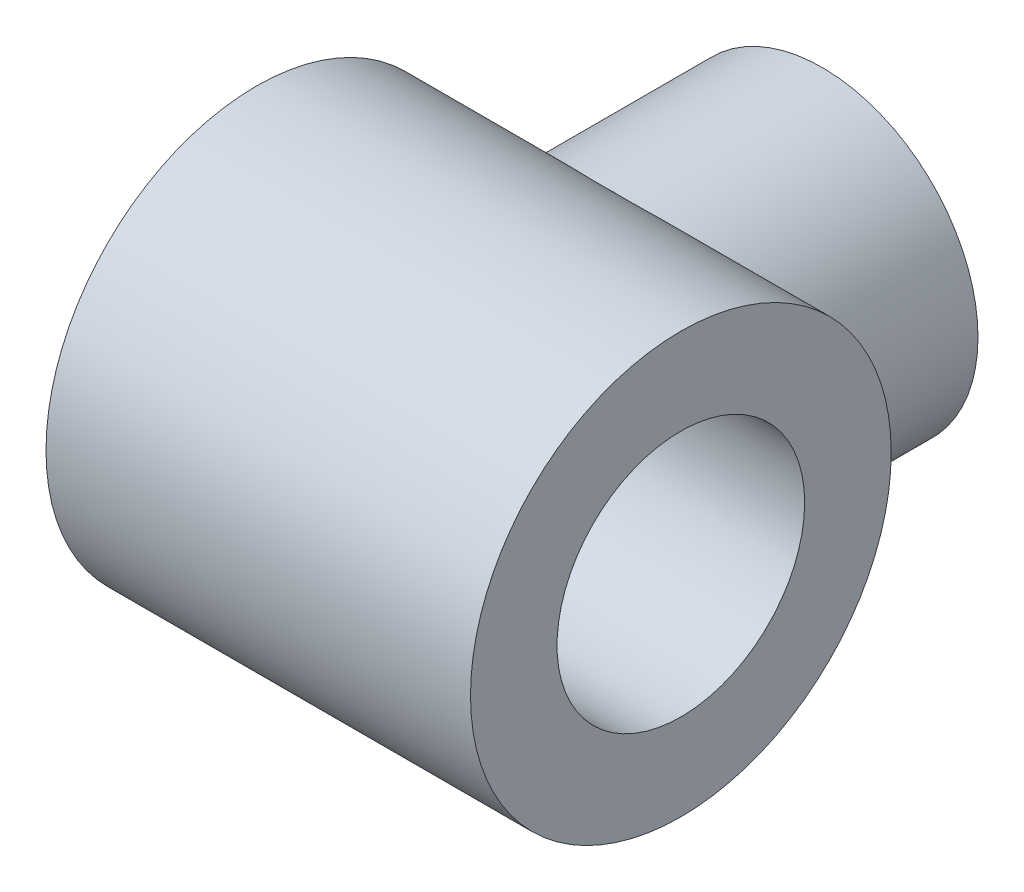
SolidWorks part; units mm, degrees
material "ABS"
ref_plane "前视基准面" through (0, 0, 0) normal (0, 0, 1) x (1, 0, 0)
ref_plane "上视基准面" through (0, 0, 0) normal (0, 1, 0) x (1, 0, 0)
ref_plane "右视基准面" through (0, 0, 0) normal (1, 0, 0) x (0, 0, -1)
sketch "草图1" plane through (0, 0, 0) normal (0, 0, 1) x (1, 0, 0)
  circle A0 centre (0, 0) radius 1.2
  circle A1 centre (0, 0) radius 2.2
  dimension "D1" = 2.4
  dimension "D2" = 4.4
extrude "凸台-拉伸1" add sketch "草图1" along normal blind 3
sketch "草图2" plane through (0, 0, 0) normal (1, 0, 0) x (0, 0, -1)
  line L0 (0, 0) -> (-5, 0) construction
  line L1 (-3, 0) -> (-3, 2.2) construction
  line L2 (-3, 2.2) -> (-3, -2.2) construction
  circle A0 centre (-5, 0) radius 2.9732
  circle A1 centre (-5, 0) radius 1.75
  dimension "D3" = 3.5
  dimension "D1" = 5
extrude "凸台-拉伸2" add sketch "草图2" along normal blind 3 and the other way blind 3 separate body
